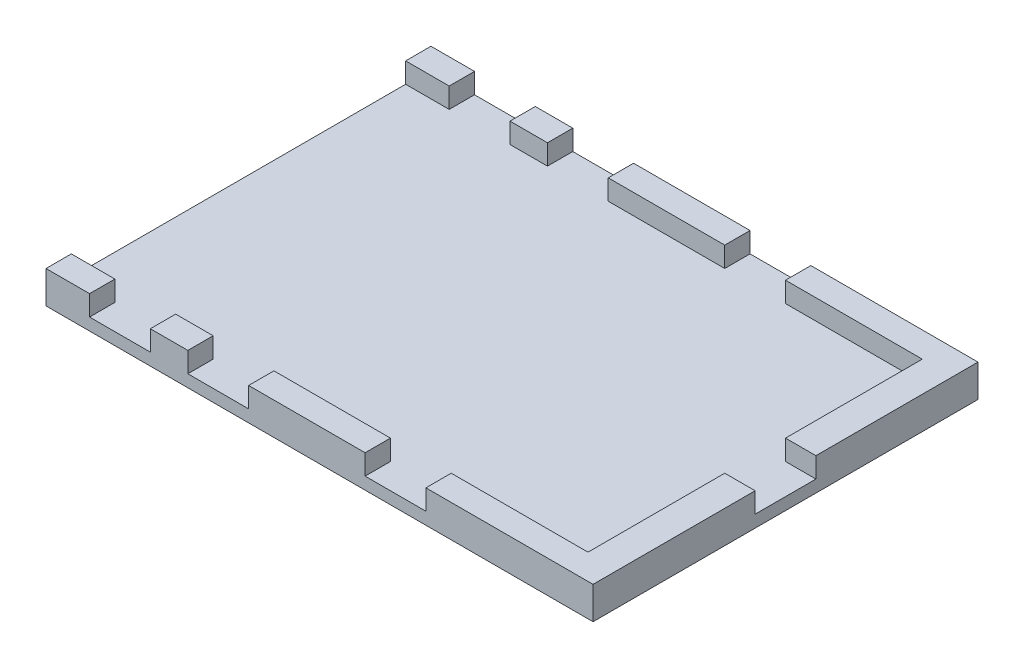
SolidWorks part; units mm, degrees
ref_plane "Front Plane" through (0, 0, 0) normal (0, 0, 1) x (1, 0, 0)
ref_plane "Top Plane" through (0, 0, 0) normal (0, 1, 0) x (1, 0, 0)
ref_plane "Right Plane" through (0, 0, 0) normal (1, 0, 0) x (0, 0, -1)
sketch "Sketch1" plane through (0, 0, 0) normal (0, 1, 0) x (1, 0, 0)
  line L1 (-27, -19) -> (27, -19)
  line L2 (-27, -19) -> (-27, 19)
  line L3 (-27, 19) -> (27, 19)
  line L4 (27, -19) -> (27, 19)
  line L5 (-27, -19) -> (27, 19) construction
  line L6 (-27, 19) -> (27, -19) construction
  point P0 (0, 0)
  dimension "D1" = 54
  dimension "D2" = 38
extrude "Boss-Extrude1" add sketch "Sketch1" along normal blind 1.2
sketch "Sketch3" plane through (0, 1.2, 0) normal (0, 1, 0) x (1, 0, 0)
  line L0 (-27, -19) -> (27, -19)
  line L1 (27, -19) -> (27, 19)
  line L2 (27, 19) -> (-27, 19)
  line L3 (-27, 19) -> (-27, 16.5)
  line L4 (-27, 16.5) -> (24, 16.5)
  line L5 (24, 16.5) -> (24, -16.5)
  line L6 (24, -16.5) -> (-27, -16.5)
  line L7 (-27, -16.5) -> (-27, -19)
  line L8 (-22.7, 16.5) -> (-22.7, 19)
  line L9 (-16.7, 16.5) -> (-16.7, 19)
  line L10 (-13, 16.5) -> (-13, 19)
  line L11 (-7, 16.5) -> (-7, 19)
  line L12 (4.5, 16.5) -> (4.5, 19)
  line L13 (10.5, 16.5) -> (10.5, 19)
  line L14 (24, 3) -> (27, 3)
  line L15 (24, -3) -> (27, -3)
  line L16 (-27, 0) -> (27, 0) construction
  line L17 (-27, 19) -> (-27, -19) construction
  line L18 (10.5, -16.5) -> (10.5, -19)
  line L19 (4.5, -19) -> (4.5, -16.5)
  line L20 (-7, -16.5) -> (-7, -19)
  line L21 (-13, -16.5) -> (-13, -19)
  line L22 (-16.7, -16.5) -> (-16.7, -19)
  line L23 (-22.7, -16.5) -> (-22.7, -19)
  point P2 (27, 0)
  point P5 (0, -19)
  point P13 (24, 0)
  dimension "D1" = 38
  dimension "D2" = 54
  dimension "D3" = 33
  dimension "D4" = 51
  dimension "D5" = 6
  dimension "D6" = 6
  dimension "D7" = 4.3
  dimension "D8" = 20
  dimension "D9" = 6
  dimension "D10" = 13.5
  dimension "D11" = 6
extrude "Boss-Extrude2" add sketch "Sketch3" along normal blind 2 contours L4 L8 L2 L3 | L4 L10 L2 L9 | L4 L12 L2 L11 | L5 L14 L1 L2 L13 L4 | L6 L18 L0 L1 L15 L5 | L6 L20 L0 L19 | L6 L22 L0 L21 | L23 L6 L7 L0 region at (-24.85, 1.2, 17.75) region at (-14.85, 1.2, 17.75) region at (-1.25, 1.2, 17.75) region at (10.7298, 1.2, 17.75) region at (25.5, 1.2, -3.2298) region at (-1.25, 1.2, -17.75) region at (-14.85, 1.2, -17.75) region at (-24.85, 1.2, -17.75)
